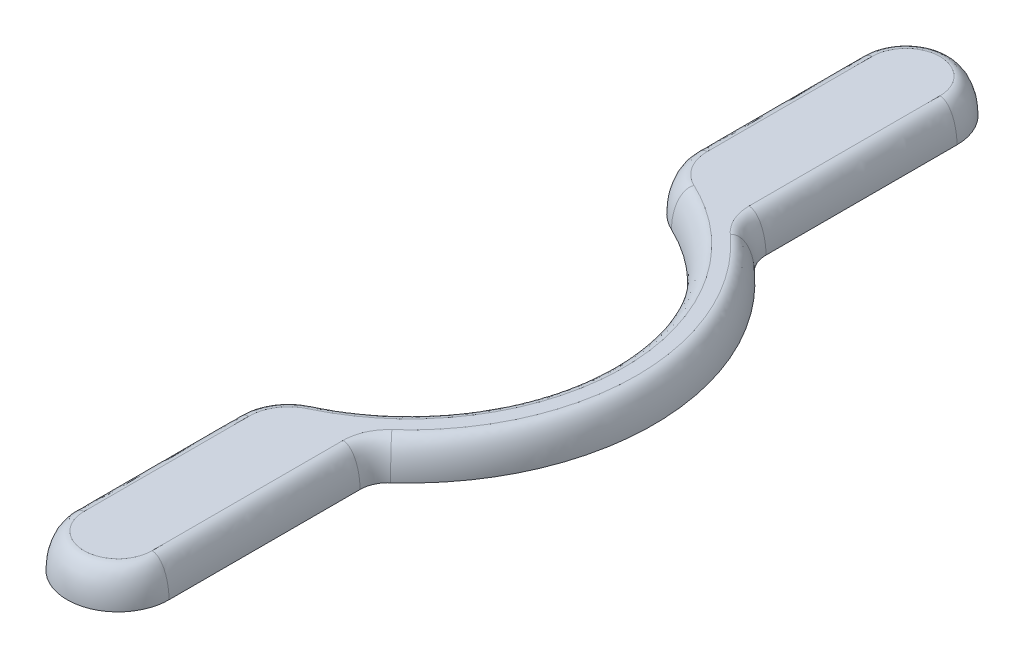
SolidWorks part; units mm, degrees
ref_plane "Alzado" through (0, 0, 0) normal (0, 0, 1) x (1, 0, 0)
ref_plane "Planta" through (0, 0, 0) normal (0, 1, 0) x (1, 0, 0)
ref_plane "Vista lateral" through (0, 0, 0) normal (1, 0, 0) x (0, 0, -1)
sketch "Croquis1" plane through (0, 0.4561, 0) normal (0, 1, 0) x (1, 0, 0)
  line L0 (40.8564, -55.1463) -> (40.8564, -18.3821) construction
  line L1 (42.1064, -55.1463) -> (42.1064, -18.3821) construction
  line L2 (42.1064, -97.2104) -> (42.1064, -60.4463) construction
  line L3 (40.8564, -97.2104) -> (40.8564, -60.4463) construction
  line L4 (40.8564, -55.1463) -> (40.8564, -18.3821) construction
  line L5 (42.1064, -55.1463) -> (42.1064, -18.3821) construction
  line L6 (42.1064, -97.2104) -> (42.1064, -60.4463) construction
  line L7 (40.8564, -97.2104) -> (40.8564, -60.4463) construction
  line L8 (42.1064, -64.7463) -> (42.1064, -61.3771)
  line L10 (40.3064, -64.7463) -> (40.3064, -61.8397)
  line L11 (42.1064, -61.1463) -> (40.3064, -61.1463) construction
  line L12 (40.8564, -60.4463) -> (42.1064, -60.4463) construction
  line L13 (42.1064, -60.4463) -> (42.1064, -55.1463) construction
  line L14 (43.7064, -57.7963) -> (39.3994, -57.7963) construction
  line L18 (41.2064, -65.6463) -> (41.2064, -64.7463) construction
  line L19 (41.2064, -64.7463) -> (40.3064, -64.7463) construction
  line L21 (42.1064, -50.8463) -> (42.1064, -54.2154)
  line L22 (40.3064, -50.8463) -> (40.3064, -53.7528)
  arc A0 (42.2728, -61.0046) -> (42.2728, -54.5879) centre (39.3994, -57.7963) ccw
  arc A1 (40.8798, -60.9353) -> (40.8798, -54.6572) centre (39.3994, -57.7963) ccw
  arc A2 (42.2728, -61.0046) -> (42.1064, -61.3771) centre (42.6064, -61.3771) ccw
  arc A6 (42.1064, -64.7463) -> (40.3064, -64.7463) centre (41.2064, -64.7463) cw
  arc A7 (42.2728, -54.5879) -> (42.1064, -54.2154) centre (42.6064, -54.2154) cw
  arc A9 (42.1064, -50.8463) -> (40.3064, -50.8463) centre (41.2064, -50.8463) ccw
  arc A10 (40.3064, -61.8397) -> (40.8798, -60.9353) centre (41.3064, -61.8397) cw
  arc A11 (40.3064, -53.7528) -> (40.8798, -54.6572) centre (41.3064, -53.7528) ccw
  point P10 (0, 0)
  point P20 (41.2064, -65.6463)
  point P21 (40.31, -54.3621)
  point P22 (42.1064, -57.7963)
  point P30 (0, 0)
  point P34 (43.7064, -57.7963)
  point P35 (0, 0)
  point P36 (40.3064, -61.1463)
  point P39 (40.3064, -54.4463)
  dimension "D4" = 0.5
  dimension "D6" = 1
  dimension "D1" = 1.8
  dimension "D2" = 4.5
  dimension "D3" = 0.7
  dimension "D5" = 3.4
extrude "Saliente-Extruir1" add sketch "Croquis1" along normal blind 0.6
fillet "Redondeo2" radius 0.6 12 edges at (40.3064, 1.0561, 52.2995) (41.2064, 1.0561, 49.9463) (42.87, 1.0561, 57.7963) (42.1064, 1.0561, 52.5308) (42.1499, 1.0561, 54.4194) (40.3064, 1.0561, 63.293) (43.7064, 1.0561, 57.7963) (41.2064, 1.0561, 65.6463) (42.1499, 1.0561, 61.1731) (42.1064, 1.0561, 63.0617) (40.4618, 1.0561, 54.2882) (40.4618, 1.0561, 61.3043) second distance 0.3 first distance on face at (40.3064, 0.7561, 52.2995) first distance on face at (41.2064, 0.7561, 50.3963) first distance on face at (41.8749, 0.7561, 57.7963) first distance on face at (42.1064, 0.7561, 52.5308) first distance on face at (42.1698, 0.7561, 54.4105) first distance on face at (40.3064, 0.7561, 63.293) first distance on face at (42.9896, 0.7561, 57.7963) first distance on face at (41.2064, 0.7561, 65.1963) first distance on face at (42.1698, 0.7561, 61.182) first distance on face at (42.1064, 0.7561, 63.0617) first distance on face at (40.5275, 0.7561, 54.2466) first distance on face at (40.5275, 0.7561, 61.3459)
sketch "Croquis2" plane through (0, 0.4561, 0) normal (0, -1, 0) x (1, 0, 0)
  line L0 (42.1064, 64.7463) -> (42.1064, 61.3771) construction
  line L1 (42.1064, 64.7463) -> (42.1064, 61.3771)
  line L2 (40.8564, 60.4602) -> (42.1064, 60.4602)
